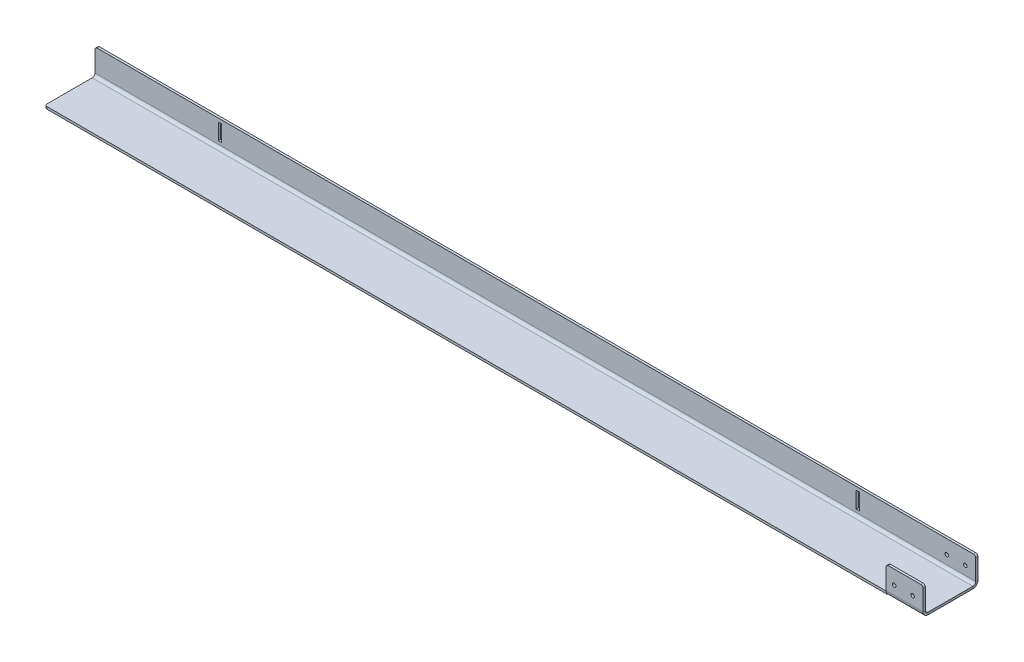
SolidWorks part; units mm, degrees
note: The reader was unsure of these and kept them because the rebuilt part matched: flange length of "Edge-Flange1", "Edge-Flange2"; thickness of "Edge-Flange1", "Edge-Flange2".
material "5052-H32"
ref_plane "Front Plane" through (0, 0, 0) normal (0, 0, 1) x (1, 0, 0)
ref_plane "Top Plane" through (0, 0, 0) normal (0, 1, 0) x (1, 0, 0)
ref_plane "Right Plane" through (0, 0, 0) normal (1, 0, 0) x (0, 0, -1)
sketch "Sketch1" plane through (0, 0, 0) normal (0, 1, 0) x (1, 0, 0)
  line L5 (-604.8375, -72.3138) -> (604.8375, -72.3138)
  line L6 (-604.8375, -72.3138) -> (-604.8375, 0)
  line L7 (-604.8375, 0) -> (604.8375, 0)
  line L8 (604.8375, -72.3138) -> (604.8375, 0)
  point P4 (0, 0)
  dimension "D1" = 1209.675
  dimension "D2" = 72.3138
base flange "Base-Flange1" sketch "Sketch1" thickness 3.175 reverse thickness direction yes parameters "D1"=3.81
edge flange "Edge-Flange1" sketch "Sketch8" flange angle 90 flange length 38.1 flange position material inside bend radius 3.81 thickness 3.175 relief rectangular parameters "D6"=10
sketch "Sketch8" plane through (0, 3.175, 0) normal (0, 0, -1) x (-1, 0, 0)
  line L2 (604.8375, 0) -> (604.8375, 34.925)
  line L3 (604.8375, 34.925) -> (-604.8375, 34.925)
  line L4 (-604.8375, 34.925) -> (-604.8375, 0)
  line L7 (-604.8375, 0) -> (604.8375, 0) construction
  line L8 (-604.8375, 0) -> (604.8375, 0)
bend "EdgeBend1" bend radius 3.81 bend angle 90 parameters "D5"=1
sketch "Sketch9" plane through (0, 0, 0) normal (0, -1, 0) x (-1, 0, 0)
  line L1 (604.8375, -6.985) -> (604.8375, -72.3138) construction
  line L2 (604.8375, -72.3138) -> (-604.8375, -72.3138) construction
  circle A0 centre (-116.6813, -37.3888) radius 21.717
  circle A2 centre (364.3312, -37.3888) radius 21.717
  dimension "D1" = 34.925
  dimension "D4" = 43.434
  dimension "D2" = 240.5062
  dimension "D3" = 481.0125
extrude "Cut-Extrude1" [suppressed] cut sketch "Sketch9" against normal through all
sketch "Sketch10" plane through (0, 0, 0) normal (0, 0, -1) x (-1, 0, 0)
  line L0 (604.8375, 6.985) -> (604.8375, 38.1) construction
  line L1 (431.2285, 33.3375) -> (435.4195, 33.3375)
  line L2 (431.2285, 33.3375) -> (431.2285, 11.1125)
  line L3 (431.2285, 11.1125) -> (435.4195, 11.1125)
  line L4 (435.4195, 33.3375) -> (435.4195, 11.1125)
  line L5 (604.8375, 38.1) -> (-604.8375, 38.1) construction
  dimension "D1" = 169.418
  dimension "D2" = 4.191
  dimension "D3" = 22.225
  dimension "D4" = 4.7625
extrude "Cut-Extrude2" cut sketch "Sketch10" against normal through all normal cut yes
fillet "Fillet1" radius 3.175 3 edges at (604.8375, 38.1, 1.5875) (-604.8375, 1.5875, 72.3138) (-604.8375, 38.1, 1.5875)
pattern_linear "LPattern1" count 2 spacing 876.173 along (1, 0, 0) of "Cut-Extrude2"
edge flange "Edge-Flange2" sketch "Sketch13" flange angle 90 flange length 38.1 flange position material outside bend radius 3.81 thickness 3.175 relief rectangular parameters "D6"=10
sketch "Sketch13" plane through (0, 3.175, 72.3138) normal (0, 0, 1) x (1, 0, 0)
  line L3 (554.0375, 34.925) -> (604.8375, 34.925)
  line L4 (604.8375, 34.925) -> (604.8375, 0)
  line L7 (-601.6625, 0) -> (604.8375, 0) construction
  line L8 (554.0375, 0) -> (604.8375, 0)
  line L9 (554.0375, 34.925) -> (554.0375, 0)
  dimension "D1" = 50.8
bend "EdgeBend2" bend radius 3.81 bend angle 90 parameters "D5"=2
fillet "Fillet2" radius 3.175 2 edges at (604.8375, 38.1, 73.9013) (554.0375, 38.1, 73.9013)
hole_wizard "#10 (0.1935) Diameter Hole1" positions "Sketch14" profile "Sketch15" hole size "#10" standard "ANSI Inch" end condition through all
sketch "Sketch14" plane through (0, 0, 75.4888) normal (0, 0, 1) x (1, 0, 0)
  line L0 (604.8375, 6.985) -> (604.8375, 34.925) construction
  line L2 (601.6625, 38.1) -> (557.2125, 38.1) construction
  point P0 (590.55, 19.05)
  point P2 (565.15, 19.05)
  dimension "D1" = 14.2875
  dimension "D2" = 25.4
  dimension "D3" = 19.05
sketch "Sketch15" plane through (590.55, 19.05, 75.4888) normal (1, 0, 0) x (0, -1, 0)
  line L0 (0, 0) -> (0, 75.4888)
  line L1 (0, 75.4888) -> (2.4574, 75.4888)
  line L2 (2.4574, 75.4888) -> (2.4574, 0)
  line L5 (2.4574, 0) -> (0, 0)
  line L11 (0, -6.35) -> (0, 107.95) construction
  dimension "Thru Hole Dia." = 4.9149
  dimension "Thru Hole Depth" = 75.4888
sketch "Bend-Lines1" [suppressed] plane through (0, 0, 0) normal (0, 1, 0) x (1, 0, 0)
sketch "Bounding-Box1" [suppressed] plane through (0, 0, 0) normal (0, 1, 0) x (1, 0, 0)
sheet metal parameters "Sheet-Metal1" thickness 3.175 parameters "D1"=3
flat pattern "Flat-Pattern1" [suppressed]
sketch "Bend-Lines2" plane through (0, 0, 0) normal (0, 1, 0) x (1, 0, 0)
sketch3d "Bounding-Box2" [suppressed]
  line L0 (-631.825, 0, 0) -> (631.825, 0, 0) construction
  line L1 (-631.825, -101.6, 0) -> (631.825, -101.6, 0) construction
  line L2 (-631.825, 0, 0) -> (-631.825, -101.6, 0) construction
  line L3 (631.825, 0, 0) -> (631.825, -101.6, 0) construction
sheet metal parameters "Sheet-Metal2" thickness 3.175 parameters "D1"=3, "D7"=3
flat pattern "Flat-Pattern1"
sketch "Bend-Lines2" plane through (0, 0, 0) normal (0, 1, 0) x (1, 0, 0)
  line L0 (631.825, -2.4657) -> (-631.825, -2.4657) construction
  line L1 (631.825, -2.4657) -> (-631.825, -2.4657) construction
sketch3d "Bounding-Box2" [suppressed]
  line L0 (631.825, 33.1686, 0) -> (-631.825, 33.1686, 0) construction
  line L1 (631.825, -101.6, 0) -> (-631.825, -101.6, 0) construction
  line L2 (631.825, 33.1686, 0) -> (631.825, -101.6, 0) construction
  line L3 (-631.825, 33.1686, 0) -> (-631.825, -101.6, 0) construction
bend of the flat pattern "Flatten-<EdgeBend1>1"
sheet metal parameters "Sheet-Metal3" thickness 3.175 parameters "D1"=3, "D7"=3
flat pattern "Flat-Pattern1"
sketch "Bend-Lines2" plane through (0, 0, 0) normal (0, -1, 0) x (-1, 0, 0)
  line L0 (631.825, -2.4657) -> (-631.825, -2.4657) construction
  line L1 (631.825, -2.4657) -> (-631.825, -2.4657) construction
sketch3d "Bounding-Box2" [suppressed]
  line L0 (-631.825, 33.1686, 0) -> (631.825, 33.1686, 0) construction
  line L1 (-631.825, -101.6, 0) -> (631.825, -101.6, 0) construction
  line L2 (-631.825, 33.1686, 0) -> (-631.825, -101.6, 0) construction
  line L3 (631.825, 33.1686, 0) -> (631.825, -101.6, 0) construction
bend of the flat pattern "Flatten-<EdgeBend1>1"
sheet metal parameters "Sheet-Metal4" thickness 3.175 parameters "D1"=3, "D7"=3
flat pattern "Flat-Pattern1"
sketch "Bend-Lines2" plane through (0, 0, 0) normal (0, -1, 0) x (-1, 0, 0)
  line L0 (609.6, -2.7458) -> (-609.6, -2.7458) construction
  line L1 (609.6, -2.7458) -> (-609.6, -2.7458) construction
sketch3d "Bounding-Box2" [suppressed]
  line L0 (609.6, 32.6068, 0) -> (-609.6, 32.6084, 0) construction
  line L1 (609.5999, -73.025, 0) -> (-609.6001, -73.0234, 0) construction
  line L2 (609.6, 32.6068, 0) -> (609.5999, -73.025, 0) construction
  line L3 (-609.6, 32.6084, 0) -> (-609.6001, -73.0234, 0) construction
bend of the flat pattern "Flatten-<EdgeBend1>1"
sheet metal parameters "Sheet-Metal6" thickness 3.175 parameters "D1"=3, "D7"=3
flat pattern "Flat-Pattern1"
sketch "Bend-Lines2" plane through (0, 0, 0) normal (0, -1, 0) x (-1, 0, 0)
  line L0 (609.6, -2.7458) -> (-609.6, -2.7458) construction
  line L1 (609.6, -2.7458) -> (-609.6, -2.7458) construction
sketch3d "Bounding-Box2" [suppressed]
  line L0 (609.6, 32.6068, 0) -> (-609.6, 32.6084, 0) construction
  line L1 (609.5999, -73.025, 0) -> (-609.6001, -73.0234, 0) construction
  line L2 (609.6, 32.6068, 0) -> (609.5999, -73.025, 0) construction
  line L3 (-609.6, 32.6084, 0) -> (-609.6001, -73.0234, 0) construction
bend of the flat pattern "Flatten-<EdgeBend1>1"
sheet metal parameters "Sheet-Metal7" thickness 3.175 parameters "D1"=3, "D7"=3
flat pattern "Flat-Pattern1"
sketch "Bend-Lines2" plane through (0, 0, 0) normal (0, -1, 0) x (-1, 0, 0)
  line L0 (609.6, -2.7458) -> (-609.6, -2.7458) construction
  line L1 (609.6, -2.7458) -> (-609.6, -2.7458) construction
  line L2 (-609.6, -73.628) -> (-558.8, -73.628) construction
  line L3 (-609.6, -73.628) -> (-558.8, -73.628) construction
sketch3d "Bounding-Box2" [suppressed]
  line L0 (609.6, 32.6068, 0) -> (-609.6, 32.6084, 0) construction
  line L1 (609.5998, -109.1575, 0) -> (-609.6002, -109.156, 0) construction
  line L2 (609.6, 32.6068, 0) -> (609.5998, -109.1575, 0) construction
  line L3 (-609.6, 32.6084, 0) -> (-609.6002, -109.156, 0) construction
bend of the flat pattern "Flatten-<EdgeBend1>1"
bend of the flat pattern "Flatten-<EdgeBend2>1"
sheet metal parameters "Sheet-Metal8" thickness 3.175 parameters "D1"=3, "D7"=3
flat pattern "Flat-Pattern1"
sketch "Bend-Lines2" plane through (0, 0, 0) normal (0, -1, 0) x (-1, 0, 0)
  line L0 (604.8375, -2.6797) -> (-604.8375, -2.6797) construction
  line L1 (604.8375, -2.6797) -> (-604.8375, -2.6797) construction
  line L2 (-604.8375, -72.8091) -> (-554.0375, -72.8091) construction
  line L3 (-604.8375, -72.8091) -> (-554.0375, -72.8091) construction
sketch3d "Bounding-Box2" [suppressed]
  line L0 (604.8375, 32.7391, 0) -> (-604.8375, 32.7406, 0) construction
  line L1 (604.8373, -108.2309, 0) -> (-604.8377, -108.2294, 0) construction
  line L2 (604.8375, 32.7391, 0) -> (604.8373, -108.2309, 0) construction
  line L3 (-604.8375, 32.7406, 0) -> (-604.8377, -108.2294, 0) construction
bend of the flat pattern "Flatten-<EdgeBend1>1"
bend of the flat pattern "Flatten-<EdgeBend2>1"
